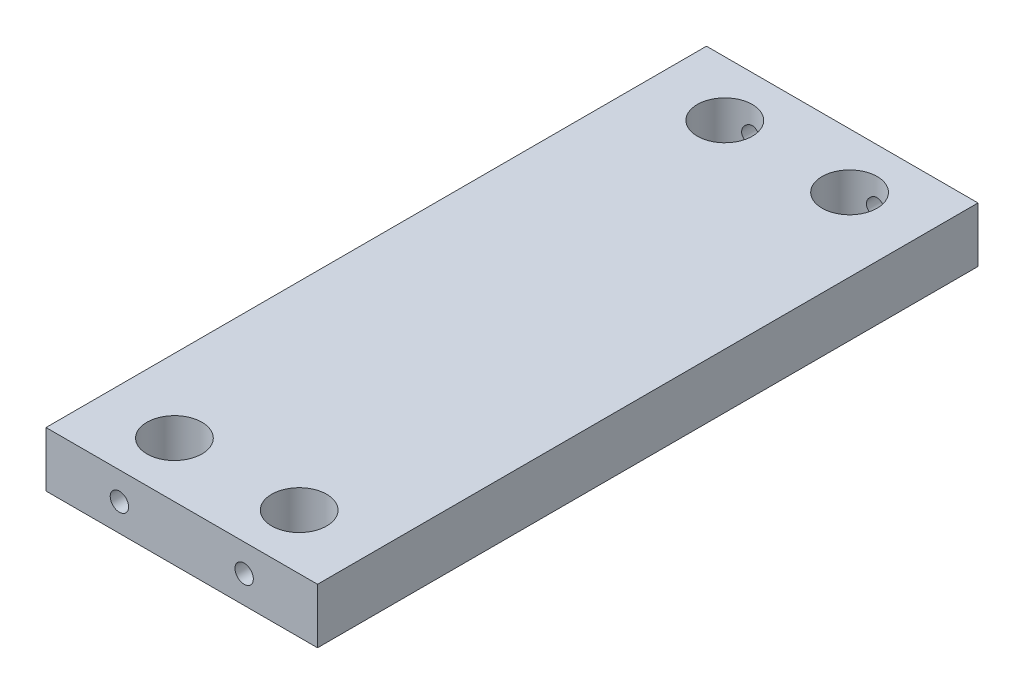
SolidWorks part; units mm, degrees
material "Pine"
ref_plane "Front Plane" through (0, 0, 0) normal (0, 0, 1) x (1, 0, 0)
ref_plane "Top Plane" through (0, 0, 0) normal (0, 1, 0) x (1, 0, 0)
ref_plane "Right Plane" through (0, 0, 0) normal (1, 0, 0) x (0, 0, -1)
sketch "Sketch1" plane through (0, 0, 0) normal (0, 1, 0) x (1, 0, 0)
  line L1 (-46.99, 114.3) -> (46.99, 114.3)
  line L2 (-46.99, 114.3) -> (-46.99, -114.3)
  line L3 (-46.99, -114.3) -> (46.99, -114.3)
  line L4 (46.99, 114.3) -> (46.99, -114.3)
  line L5 (-46.99, 114.3) -> (46.99, -114.3) construction
  line L6 (-46.99, -114.3) -> (46.99, 114.3) construction
  point P0 (0, 0)
  dimension "D1" = 228.6
  dimension "D2" = 93.98
extrude "Boss-Extrude1" add sketch "Sketch1" along normal blind 19.05
hole_wizard "3/4 (0.75) Diameter Hole1" positions "Sketch3" profile "Sketch2" hole size "3/4" standard "Ansi Inch"
sketch "Sketch3" plane through (0, 19.05, 0) normal (0, 1, 0) x (-1, 0, 0)
  line L0 (46.99, -114.3) -> (46.99, 114.3) construction
  line L1 (-46.99, -114.3) -> (46.99, -114.3) construction
  point P0 (21.59, -95.25)
  dimension "D1" = 25.4
  dimension "D2" = 19.05
sketch "Sketch2" plane through (-21.59, 19.05, -95.25) normal (1, 0, 0) x (0, 0, 1)
  line L0 (0, 0) -> (0, 24.7732)
  line L1 (0, 24.7732) -> (9.525, 19.05)
  line L2 (9.525, 19.05) -> (9.525, 0)
  line L5 (9.525, 0) -> (0, 0)
  line L10 (0, 24.7732) -> (-9.525, 19.05) construction
  line L11 (0, -6.35) -> (0, 107.95) construction
  dimension "Hole Dia." = 19.05
  dimension "Hole Depth" = 19.05
  dimension "Drill Angle" = 118
mirror "Mirror1" about plane through (0, 0, 0) normal (0, 0, 1) of "3/4 (0.75) Diameter Hole1"
mirror "Mirror4" about plane through (0, 0, 0) normal (1, 0, 0) of "Mirror1", "3/4 (0.75) Diameter Hole1"
hole_wizard "1/4 (0.25) Diameter Hole1" positions "Sketch5" profile "Sketch4" hole size "1/4" standard "Ansi Inch"
sketch "Sketch5" plane through (0, 0, -114.3) normal (0, 0, -1) x (-1, 0, 0)
  line L0 (-46.99, 19.05) -> (-46.99, 0) construction
  line L1 (-46.99, 0) -> (46.99, 0) construction
  point P0 (-21.59, 9.525)
  dimension "D1" = 25.4
  dimension "D2" = 9.525
sketch "Sketch4" plane through (21.59, 9.525, -114.3) normal (1, 0, 0) x (0, 1, 0)
  line L0 (0, 0) -> (0, 20.9577)
  line L1 (0, 20.9577) -> (3.175, 19.05)
  line L2 (3.175, 19.05) -> (3.175, 0)
  line L5 (3.175, 0) -> (0, 0)
  line L10 (0, 20.9577) -> (-3.175, 19.05) construction
  line L11 (0, -6.35) -> (0, 107.95) construction
  dimension "Hole Dia." = 6.35
  dimension "Hole Depth" = 19.05
  dimension "Drill Angle" = 118
mirror "Mirror5" about plane through (0, 0, 0) normal (0, 0, 1) of "1/4 (0.25) Diameter Hole1"
mirror "Mirror10" about plane through (0, 0, 0) normal (1, 0, 0) of "Mirror5"
